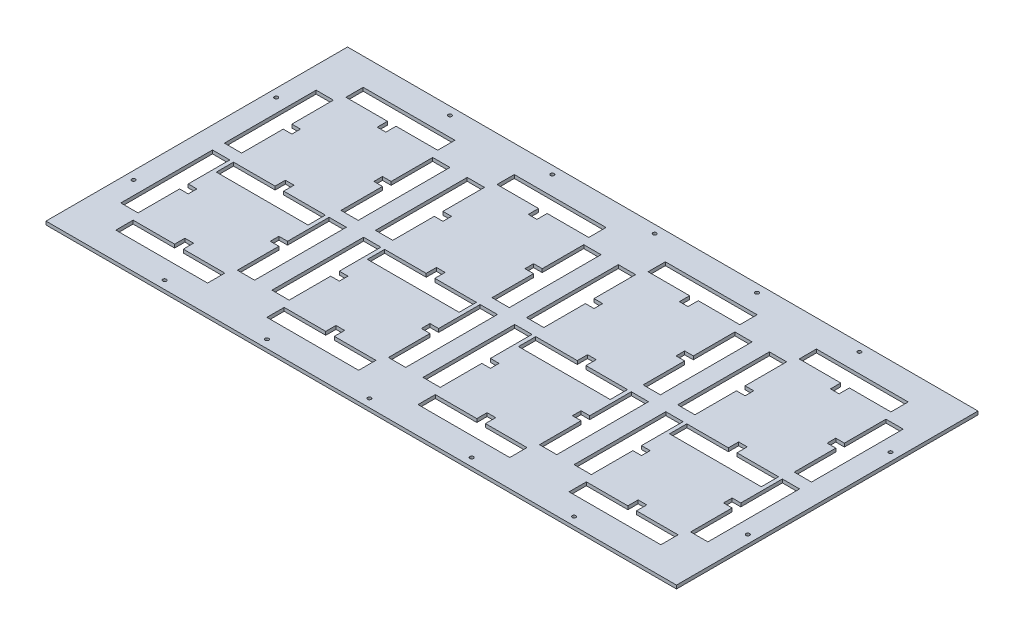
SolidWorks part; units mm, degrees
ref_plane "Front Plane" through (0, 0, 0) normal (0, 0, 1) x (1, 0, 0)
ref_plane "Top Plane" through (0, 0, 0) normal (0, 1, 0) x (1, 0, 0)
ref_plane "Right Plane" through (0, 0, 0) normal (1, 0, 0) x (0, 0, -1)
sketch "Sketch1" plane through (0, 0, 0) normal (0, 1, 0) x (1, 0, 0)
  line L0 (0, 139.7) -> (0, -139.7) construction
  line L1 (-292.1, 139.7) -> (292.1, 139.7)
  line L2 (-292.1, 139.7) -> (-292.1, -139.7)
  line L3 (-292.1, -139.7) -> (292.1, -139.7)
  line L4 (292.1, 139.7) -> (292.1, -139.7)
  line L5 (-292.1, 139.7) -> (292.1, -139.7) construction
  line L6 (-292.1, -139.7) -> (292.1, 139.7) construction
  line L7 (-284.6, 132.2) -> (284.6, 132.2) construction
  line L8 (-284.6, 132.2) -> (-284.6, -132.2) construction
  line L9 (-284.6, -132.2) -> (284.6, -132.2) construction
  line L10 (284.6, 132.2) -> (284.6, -132.2) construction
  line L11 (-284.6, 132.2) -> (284.6, -132.2) construction
  line L12 (-284.6, -132.2) -> (284.6, 132.2) construction
  line L13 (-292.1, 0) -> (292.1, 0) construction
  line L14 (284.6, 132.2) -> (284.6, -132.2) construction
  circle A0 centre (-284.6, 66.1) radius 1.65
  circle A1 centre (-189.7333, 132.2) radius 1.65
  circle A2 centre (-94.8667, 132.2) radius 1.65
  circle A3 centre (-284.6, -66.1) radius 1.65
  circle A4 centre (-94.8667, -132.2) radius 1.65
  circle A5 centre (-189.7333, -132.2) radius 1.65
  circle A6 centre (189.7333, -132.2) radius 1.65
  circle A7 centre (94.8667, -132.2) radius 1.65
  circle A8 centre (94.8667, 132.2) radius 1.65
  circle A9 centre (189.7333, 132.2) radius 1.65
  circle A10 centre (284.6, -66.1) radius 1.65
  circle A11 centre (284.6, 66.1) radius 1.65
  circle A12 centre (0, 132.2) radius 1.65
  circle A13 centre (0, -132.2) radius 1.65
  point P0 (0, 0)
  point P6 (0, 0)
  dimension "D5" = 3.3
  dimension "D6" = 3.3
  dimension "D7" = 3.3
  dimension "D12" = 3.3
  dimension "D13" = 3.3
  dimension "D1" = 584.2
  dimension "D2" = 279.4
  dimension "D3" = 7.5
  dimension "D4" = 7.5
  dimension "D8" = 66.1
  dimension "D9" = 94.8667
  dimension "D10" = 94.8667
  dimension "D11" = 94.8667
extrude "Boss-Extrude1" add sketch "Sketch1" along normal blind 3.175
sketch "Sketch2" plane through (0, 3.175, 0) normal (0, 1, 0) x (1, 0, 0)
  line L0 (0, 139.7) -> (0, -139.7) construction
  line L1 (292.1, 139.7) -> (-292.1, 139.7) construction
  line L2 (-292.1, -139.7) -> (292.1, -139.7) construction
  line L3 (-190, 139.7) -> (-190, -139.7) construction
  line L4 (-252, 139.7) -> (-252, -139.7) construction
  line L5 (-292.1, 0) -> (292.1, 0) construction
  line L6 (-292.1, 139.7) -> (-292.1, -139.7) construction
  line L7 (292.1, -139.7) -> (292.1, 139.7) construction
  line L8 (-248, 52) -> (-256, 52)
  line L12 (-248, 52) -> (-248, 44)
  line L13 (-210, 139.7) -> (-210, -139.7) construction
  line L14 (-164, 44) -> (-164, 5.5)
  line L15 (-272, 90.5) -> (-256, 90.5)
  line L16 (-272, 90.5) -> (-272, 5.5)
  line L17 (-272, 5.5) -> (-256, 5.5)
  line L19 (-172, 44) -> (-164, 44)
  line L20 (-164, 52) -> (-164, 90.5)
  line L21 (-256, 52) -> (-256, 90.5)
  line L22 (-248, 44) -> (-256, 44)
  line L23 (-256, 44) -> (-256, 5.5)
  line L24 (-148, 5.5) -> (-164, 5.5)
  line L25 (-148, 90.5) -> (-148, 5.5)
  line L26 (-148, 90.5) -> (-164, 90.5)
  line L27 (-172, 52) -> (-172, 44)
  line L28 (-172, 52) -> (-164, 52)
  line L29 (-172, -52) -> (-164, -52)
  line L30 (-172, -52) -> (-172, -44)
  line L31 (-148, -90.5) -> (-164, -90.5)
  line L32 (-148, -90.5) -> (-148, -5.5)
  line L33 (-148, -5.5) -> (-164, -5.5)
  line L34 (-256, -44) -> (-256, -5.5)
  line L35 (-248, -44) -> (-256, -44)
  line L36 (-256, -52) -> (-256, -90.5)
  line L37 (-164, -52) -> (-164, -90.5)
  line L38 (-172, -44) -> (-164, -44)
  line L39 (-272, -5.5) -> (-256, -5.5)
  line L40 (-272, -90.5) -> (-272, -5.5)
  line L41 (-272, -90.5) -> (-256, -90.5)
  line L42 (-164, -44) -> (-164, -5.5)
  line L43 (-248, -52) -> (-248, -44)
  line L44 (-248, -52) -> (-256, -52)
  line L45 (-214, 4) -> (-206, 4)
  line L46 (-206, 4) -> (-206, -5.5)
  line L47 (-206, -5.5) -> (-167.5, -5.5)
  line L48 (-167.5, -5.5) -> (-167.5, -21.5)
  line L49 (-167.5, -21.5) -> (-252.5, -21.5)
  line L50 (-252.5, -21.5) -> (-252.5, -5.5)
  line L51 (-252.5, -5.5) -> (-214, -5.5)
  line L52 (-214, -5.5) -> (-214, 4)
  line L53 (-292.1, 46.55) -> (292.1, 46.55) construction
  line L54 (-214, 98.6) -> (-214, 89.1)
  line L55 (-252.5, 98.6) -> (-214, 98.6)
  line L56 (-252.5, 114.6) -> (-252.5, 98.6)
  line L57 (-167.5, 114.6) -> (-252.5, 114.6)
  line L58 (-167.5, 98.6) -> (-167.5, 114.6)
  line L59 (-206, 98.6) -> (-167.5, 98.6)
  line L60 (-206, 89.1) -> (-206, 98.6)
  line L61 (-214, 89.1) -> (-206, 89.1)
  line L62 (-214, -89.1) -> (-206, -89.1)
  line L63 (-206, -89.1) -> (-206, -98.6)
  line L64 (-206, -98.6) -> (-167.5, -98.6)
  line L65 (-167.5, -98.6) -> (-167.5, -114.6)
  line L66 (-167.5, -114.6) -> (-252.5, -114.6)
  line L67 (-252.5, -114.6) -> (-252.5, -98.6)
  line L68 (-252.5, -98.6) -> (-214, -98.6)
  line L69 (-214, -98.6) -> (-214, -89.1)
  line L70 (-140, 139.7) -> (-140, -139.7) construction
  line L71 (-66, -98.6) -> (-66, -89.1)
  line L72 (-27.5, -98.6) -> (-66, -98.6)
  line L73 (-27.5, -114.6) -> (-27.5, -98.6)
  line L74 (-112.5, -114.6) -> (-27.5, -114.6)
  line L75 (-112.5, -98.6) -> (-112.5, -114.6)
  line L76 (-74, -98.6) -> (-112.5, -98.6)
  line L77 (-74, -89.1) -> (-74, -98.6)
  line L78 (-66, -89.1) -> (-74, -89.1)
  line L79 (-66, 89.1) -> (-74, 89.1)
  line L80 (-74, 89.1) -> (-74, 98.6)
  line L81 (-74, 98.6) -> (-112.5, 98.6)
  line L82 (-112.5, 98.6) -> (-112.5, 114.6)
  line L83 (-112.5, 114.6) -> (-27.5, 114.6)
  line L84 (-27.5, 114.6) -> (-27.5, 98.6)
  line L85 (-27.5, 98.6) -> (-66, 98.6)
  line L86 (-66, 98.6) -> (-66, 89.1)
  line L87 (-66, -5.5) -> (-66, 4)
  line L88 (-27.5, -5.5) -> (-66, -5.5)
  line L89 (-27.5, -21.5) -> (-27.5, -5.5)
  line L90 (-112.5, -21.5) -> (-27.5, -21.5)
  line L91 (-112.5, -5.5) -> (-112.5, -21.5)
  line L92 (-74, -5.5) -> (-112.5, -5.5)
  line L93 (-74, 4) -> (-74, -5.5)
  line L94 (-66, 4) -> (-74, 4)
  line L95 (-32, -52) -> (-24, -52)
  line L96 (-32, -52) -> (-32, -44)
  line L97 (-116, -44) -> (-116, -5.5)
  line L98 (-8, -90.5) -> (-24, -90.5)
  line L99 (-8, -90.5) -> (-8, -5.5)
  line L100 (-8, -5.5) -> (-24, -5.5)
  line L101 (-108, -44) -> (-116, -44)
  line L102 (-116, -52) -> (-116, -90.5)
  line L103 (-24, -52) -> (-24, -90.5)
  line L104 (-32, -44) -> (-24, -44)
  line L105 (-24, -44) -> (-24, -5.5)
  line L106 (-132, -5.5) -> (-116, -5.5)
  line L107 (-132, -90.5) -> (-132, -5.5)
  line L108 (-132, -90.5) -> (-116, -90.5)
  line L109 (-108, -52) -> (-108, -44)
  line L110 (-108, -52) -> (-116, -52)
  line L111 (-108, 52) -> (-116, 52)
  line L112 (-108, 52) -> (-108, 44)
  line L113 (-132, 90.5) -> (-116, 90.5)
  line L114 (-132, 90.5) -> (-132, 5.5)
  line L115 (-132, 5.5) -> (-116, 5.5)
  line L116 (-24, 44) -> (-24, 5.5)
  line L117 (-32, 44) -> (-24, 44)
  line L118 (-24, 52) -> (-24, 90.5)
  line L119 (-116, 52) -> (-116, 90.5)
  line L120 (-108, 44) -> (-116, 44)
  line L121 (-8, 5.5) -> (-24, 5.5)
  line L122 (-8, 90.5) -> (-8, 5.5)
  line L123 (-8, 90.5) -> (-24, 90.5)
  line L124 (-116, 44) -> (-116, 5.5)
  line L125 (-32, 52) -> (-32, 44)
  line L126 (-32, 52) -> (-24, 52)
  line L127 (32, 52) -> (24, 52)
  line L128 (32, 52) -> (32, 44)
  line L129 (116, 44) -> (116, 5.5)
  line L130 (8, 90.5) -> (24, 90.5)
  line L131 (8, 90.5) -> (8, 5.5)
  line L132 (8, 5.5) -> (24, 5.5)
  line L133 (108, 44) -> (116, 44)
  line L134 (116, 52) -> (116, 90.5)
  line L135 (24, 52) -> (24, 90.5)
  line L136 (32, 44) -> (24, 44)
  line L137 (24, 44) -> (24, 5.5)
  line L138 (132, 5.5) -> (116, 5.5)
  line L139 (132, 90.5) -> (132, 5.5)
  line L140 (132, 90.5) -> (116, 90.5)
  line L141 (108, 52) -> (108, 44)
  line L142 (108, 52) -> (116, 52)
  line L143 (108, -52) -> (116, -52)
  line L144 (108, -52) -> (108, -44)
  line L145 (132, -90.5) -> (116, -90.5)
  line L146 (132, -90.5) -> (132, -5.5)
  line L147 (132, -5.5) -> (116, -5.5)
  line L148 (24, -44) -> (24, -5.5)
  line L149 (32, -44) -> (24, -44)
  line L150 (24, -52) -> (24, -90.5)
  line L151 (116, -52) -> (116, -90.5)
  line L152 (108, -44) -> (116, -44)
  line L153 (8, -5.5) -> (24, -5.5)
  line L154 (8, -90.5) -> (8, -5.5)
  line L155 (8, -90.5) -> (24, -90.5)
  line L156 (116, -44) -> (116, -5.5)
  line L157 (32, -52) -> (32, -44)
  line L158 (32, -52) -> (24, -52)
  line L159 (66, 4) -> (74, 4)
  line L160 (74, 4) -> (74, -5.5)
  line L161 (74, -5.5) -> (112.5, -5.5)
  line L162 (112.5, -5.5) -> (112.5, -21.5)
  line L163 (112.5, -21.5) -> (27.5, -21.5)
  line L164 (27.5, -21.5) -> (27.5, -5.5)
  line L165 (27.5, -5.5) -> (66, -5.5)
  line L166 (66, -5.5) -> (66, 4)
  line L167 (66, 98.6) -> (66, 89.1)
  line L168 (27.5, 98.6) -> (66, 98.6)
  line L169 (27.5, 114.6) -> (27.5, 98.6)
  line L170 (112.5, 114.6) -> (27.5, 114.6)
  line L171 (112.5, 98.6) -> (112.5, 114.6)
  line L172 (74, 98.6) -> (112.5, 98.6)
  line L173 (74, 89.1) -> (74, 98.6)
  line L174 (66, 89.1) -> (74, 89.1)
  line L175 (66, -89.1) -> (74, -89.1)
  line L176 (74, -89.1) -> (74, -98.6)
  line L177 (74, -98.6) -> (112.5, -98.6)
  line L178 (112.5, -98.6) -> (112.5, -114.6)
  line L179 (112.5, -114.6) -> (27.5, -114.6)
  line L180 (27.5, -114.6) -> (27.5, -98.6)
  line L181 (27.5, -98.6) -> (66, -98.6)
  line L182 (66, -98.6) -> (66, -89.1)
  line L183 (214, -98.6) -> (214, -89.1)
  line L184 (252.5, -98.6) -> (214, -98.6)
  line L185 (252.5, -114.6) -> (252.5, -98.6)
  line L186 (167.5, -114.6) -> (252.5, -114.6)
  line L187 (167.5, -98.6) -> (167.5, -114.6)
  line L188 (206, -98.6) -> (167.5, -98.6)
  line L189 (206, -89.1) -> (206, -98.6)
  line L190 (214, -89.1) -> (206, -89.1)
  line L191 (214, 89.1) -> (206, 89.1)
  line L192 (206, 89.1) -> (206, 98.6)
  line L193 (206, 98.6) -> (167.5, 98.6)
  line L194 (167.5, 98.6) -> (167.5, 114.6)
  line L195 (167.5, 114.6) -> (252.5, 114.6)
  line L196 (252.5, 114.6) -> (252.5, 98.6)
  line L197 (252.5, 98.6) -> (214, 98.6)
  line L198 (214, 98.6) -> (214, 89.1)
  line L199 (214, -5.5) -> (214, 4)
  line L200 (252.5, -5.5) -> (214, -5.5)
  line L201 (252.5, -21.5) -> (252.5, -5.5)
  line L202 (167.5, -21.5) -> (252.5, -21.5)
  line L203 (167.5, -5.5) -> (167.5, -21.5)
  line L204 (206, -5.5) -> (167.5, -5.5)
  line L205 (206, 4) -> (206, -5.5)
  line L206 (214, 4) -> (206, 4)
  line L207 (248, -52) -> (256, -52)
  line L208 (248, -52) -> (248, -44)
  line L209 (164, -44) -> (164, -5.5)
  line L210 (272, -90.5) -> (256, -90.5)
  line L211 (272, -90.5) -> (272, -5.5)
  line L212 (272, -5.5) -> (256, -5.5)
  line L213 (172, -44) -> (164, -44)
  line L214 (164, -52) -> (164, -90.5)
  line L215 (256, -52) -> (256, -90.5)
  line L216 (248, -44) -> (256, -44)
  line L217 (256, -44) -> (256, -5.5)
  line L218 (148, -5.5) -> (164, -5.5)
  line L219 (148, -90.5) -> (148, -5.5)
  line L220 (148, -90.5) -> (164, -90.5)
  line L221 (172, -52) -> (172, -44)
  line L222 (172, -52) -> (164, -52)
  line L223 (172, 52) -> (164, 52)
  line L224 (172, 52) -> (172, 44)
  line L225 (148, 90.5) -> (164, 90.5)
  line L226 (148, 90.5) -> (148, 5.5)
  line L227 (148, 5.5) -> (164, 5.5)
  line L228 (256, 44) -> (256, 5.5)
  line L229 (248, 44) -> (256, 44)
  line L230 (256, 52) -> (256, 90.5)
  line L231 (164, 52) -> (164, 90.5)
  line L232 (172, 44) -> (164, 44)
  line L233 (272, 5.5) -> (256, 5.5)
  line L234 (272, 90.5) -> (272, 5.5)
  line L235 (272, 90.5) -> (256, 90.5)
  line L236 (164, 44) -> (164, 5.5)
  line L237 (248, 52) -> (248, 44)
  line L238 (248, 52) -> (256, 52)
  point P16 (-248, 48)
  point P18 (-252, 52)
  point P36 (-172, 48)
  point P53 (-172, -48)
  point P54 (-248, -48)
  point P63 (-210, 4)
  point P140 (-32, -48)
  point P141 (-108, -48)
  point P142 (-108, 48)
  point P143 (-32, 48)
  point P256 (32, 48)
  point P257 (108, 48)
  point P258 (108, -48)
  point P259 (32, -48)
  point P260 (248, -48)
  point P261 (172, -48)
  point P262 (172, 48)
  point P263 (248, 48)
  dimension "D1" = 190
  dimension "D2" = 62
  dimension "D4" = 85
  dimension "D5" = 8
  dimension "D6" = 48
  dimension "D7" = 16
  dimension "D8" = 4
  dimension "D3" = 42
  dimension "D9" = 4
  dimension "D10" = 46.55
  dimension "D11" = 50
extrude "Cut-Extrude1" cut sketch "Sketch2" against normal up to surface (3.175 mm away) up to face at (0, 0, 0)
equation "\"D6@Sketch1\"=\"D5@Sketch1\""
equation "\"D7@Sketch1\"=\"D5@Sketch1\""
equation "\"D10@Sketch1\"=\"D9@Sketch1\""
equation "\"D12@Sketch1\"=\"D5@Sketch1\""
equation "\"D13@Sketch1\"=\"D5@Sketch1\""
equation "\"D9@Sketch2\"=\"D8@Sketch2\""
